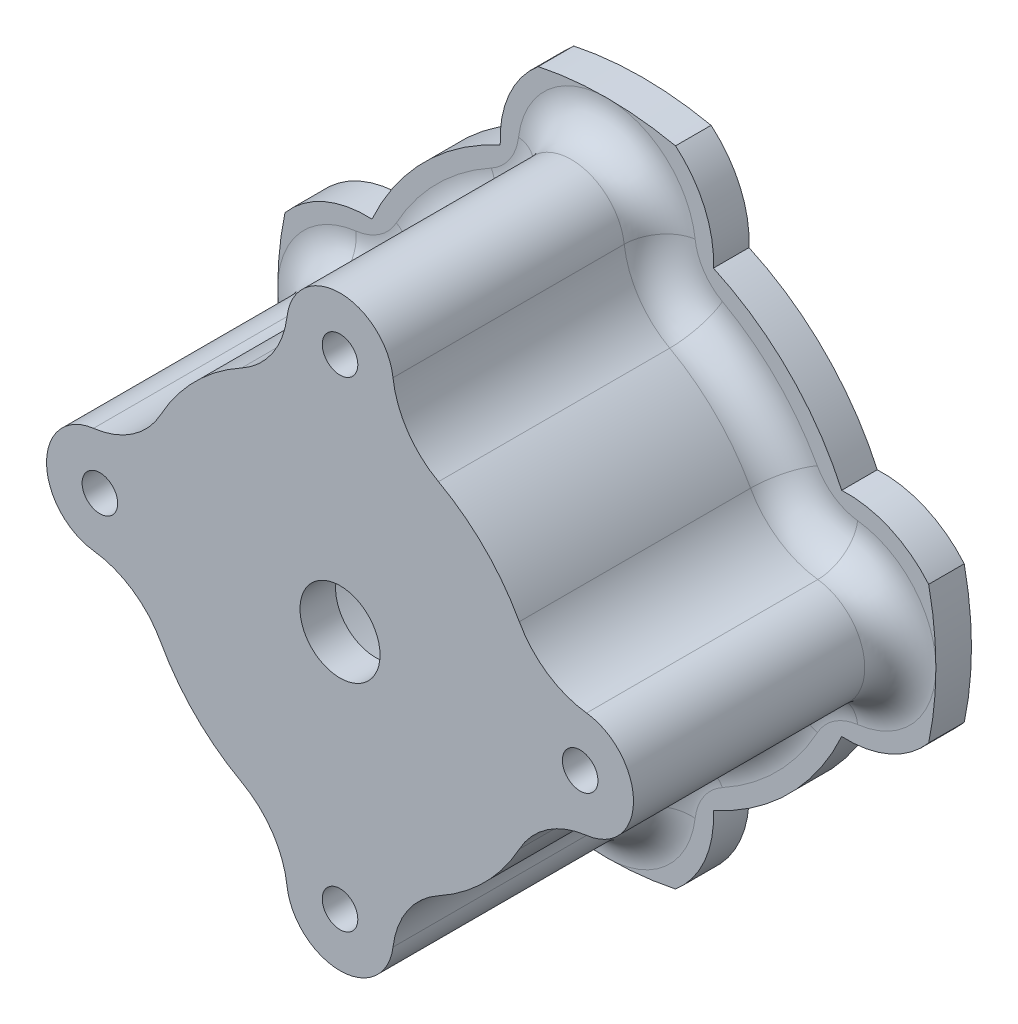
SolidWorks part; units mm, degrees
note: The reader was unsure of these and kept them because the rebuilt part matched: shared geometry of "Sketch2<3>".
ref_plane "Front Plane" through (0, 0, 0) normal (0, 0, 1) x (1, 0, 0)
ref_plane "Top Plane" through (0, 0, 0) normal (0, 1, 0) x (1, 0, 0)
ref_plane "Right Plane" through (0, 0, 0) normal (1, 0, 0) x (0, 0, -1)
sketch "Sketch1" plane through (0, 0, 3) normal (0, 0, 1) x (1, 0, 0)
  line L0 (0, 0) -> (18.5, 0) construction
  line L1 (0, 0) -> (0, -18.5) construction
  circle A1 centre (0, 0) radius 9.5
  circle A6 centre (13.5, 0) radius 1
  circle A7 centre (0, 13.5) radius 1
  circle A8 centre (-13.5, 0) radius 1
  circle A9 centre (0, -13.5) radius 1
  circle A10 centre (0, 13.5) radius 3
  circle A16 centre (-13.5, 0) radius 3
  arc A17 (-3.8611, -18.0926) -> (3.8611, -18.0926) centre (0, 0) ccw
  arc A18 (3.8611, -18.0926) -> (5.9927, -13.2037) centre (0, -13.5) ccw
  arc A19 (5.9927, -13.2037) -> (13.2037, -5.9927) centre (0, 0) ccw
  arc A20 (13.2037, -5.9927) -> (18.0926, -3.8611) centre (13.5, 0) ccw
  arc A21 (18.0926, -3.8611) -> (18.0926, 3.8611) centre (0, 0) ccw
  arc A22 (-18.0926, -3.8611) -> (-18.0926, 3.8611) centre (0, 0) cw
  arc A23 (-13.2037, -5.9927) -> (-18.0926, -3.8611) centre (-13.5, 0) cw
  arc A24 (-5.9927, -13.2037) -> (-13.2037, -5.9927) centre (0, 0) cw
  arc A25 (-3.8611, -18.0926) -> (-5.9927, -13.2037) centre (0, -13.5) cw
  arc A26 (13.2037, 5.9927) -> (18.0926, 3.8611) centre (13.5, 0) cw
  arc A27 (5.9927, 13.2037) -> (13.2037, 5.9927) centre (0, 0) cw
  arc A28 (3.8611, 18.0926) -> (5.9927, 13.2037) centre (0, 13.5) cw
  arc A29 (-3.8611, 18.0926) -> (3.8611, 18.0926) centre (0, 0) cw
  arc A30 (-3.8611, 18.0926) -> (-5.9927, 13.2037) centre (0, 13.5) ccw
  arc A31 (-5.9927, 13.2037) -> (-13.2037, 5.9927) centre (0, 0) ccw
  arc A32 (-13.2037, 5.9927) -> (-18.0926, 3.8611) centre (-13.5, 0) ccw
  circle A33 centre (0, -13.5) radius 3
  circle A34 centre (13.5, 0) radius 3
  circle A35 centre (0, 0) radius 11.5
  circle A36 centre (0, 0) radius 2.25
  dimension "D4" = 4.5
  dimension "D5" = 19
  dimension "D6" = 23
  dimension "D1" = 0
  dimension "D2" = 0
  dimension "D11" = 3.8611
  dimension "D12" = 13.2037
other "AlignGroup1"
other "AlignGroup2"
other "AlignGroup3" parameters "D2"=5.6057, "D3"=6, "D4"=4.5, "D5"=19, "D6"=23, "D7"=2, "D8"=18.5, "D9"=6, "D10"=14.5, "D1"=0, "D11"=3.8611, "D12"=5.9927, "D13"=13.2037, "D14"=13.5, "D15"=18.0926, "D16"=3.8611, "D17"=5.9927, "D18"=13.2037, "D19"=13.5, "D20"=18.0926
other "AlignGroup4"
extrude "Boss-Extrude1" add sketch "Sketch1" along normal blind 2 contours A34 A35 A10 A16 A33 A1 | A16 A35 | A35 A16 A8 | A35 A34 A6 | A35 A33 A9 | A33 A35 | A10 A35 | A35 A10 A7 | A31 A32 A22 A23 A24 A25 A17 A18 A19 A20 A21 A26 A27 A28 A29 A30 A35 A34 A33 A16 A10
sketch "Sketch2" plane through (0, 0, 5) normal (0, 0, 1) x (1, 0, 0)
  arc A0 (-5.5352, 10.0802) -> (-10.0802, 5.5352) centre (0, 0) ccw
  circle A1 centre (0, -13.5) radius 1
  circle A2 centre (0, -13.5) radius 1
  circle A3 centre (-13.5, 0) radius 1
  circle A4 centre (-13.5, 0) radius 1
  circle A5 centre (0, 13.5) radius 1
  circle A6 centre (0, 13.5) radius 1
  circle A7 centre (13.5, 0) radius 1
  circle A8 centre (13.5, 0) radius 1
  circle A9 centre (0, 0) radius 9.5
  circle A10 centre (0, 0) radius 9.5
  circle A11 centre (0, 0) radius 11.5
  arc A12 (-10.0802, -5.5352) -> (-5.5352, -10.0802) centre (0, 0) ccw
  circle A13 centre (13.5, 0) radius 3
  arc A14 (13.8611, -2.9782) -> (13.8611, 2.9782) centre (13.5, 0) ccw
  circle A15 centre (0, -13.5) radius 3
  arc A16 (-2.9782, -13.8611) -> (2.9782, -13.8611) centre (0, -13.5) ccw
  circle A17 centre (-13.5, 0) radius 3
  arc A18 (-13.8611, 2.9782) -> (-13.8611, -2.9782) centre (-13.5, 0) ccw
  circle A19 centre (0, 13.5) radius 3
  arc A20 (2.9782, 13.8611) -> (-2.9782, 13.8611) centre (0, 13.5) ccw
  circle A21 centre (0, 0) radius 2.25
  circle A22 centre (0, 0) radius 2.25
  arc A23 (10.0802, 5.5352) -> (5.5352, 10.0802) centre (0, 0) ccw
  arc A24 (5.5352, -10.0802) -> (10.0802, -5.5352) centre (0, 0) ccw
  arc A25 (-13.8611, -2.9782) -> (-10.0802, -5.5352) centre (-14.463, -7.9418) cw
  arc A26 (-13.8611, 2.9782) -> (-10.0802, 5.5352) centre (-14.463, 7.9418) ccw
  arc A27 (-2.9782, -13.8611) -> (-5.5352, -10.0802) centre (-7.9418, -14.463) ccw
  arc A28 (2.9782, -13.8611) -> (5.5352, -10.0802) centre (7.9418, -14.463) cw
  arc A29 (13.8611, -2.9782) -> (10.0802, -5.5352) centre (14.463, -7.9418) ccw
  arc A30 (13.8611, 2.9782) -> (10.0802, 5.5352) centre (14.463, 7.9418) cw
  arc A31 (-2.9782, 13.8611) -> (-5.5352, 10.0802) centre (-7.9418, 14.463) cw
  arc A32 (-3.8611, -18.0926) -> (3.8611, -18.0926) centre (0, 0) ccw
  arc A33 (3.8611, -18.0926) -> (5.9927, -13.2037) centre (0, -13.5) ccw
  arc A34 (5.9927, -13.2037) -> (13.2037, -5.9927) centre (0, 0) ccw
  arc A35 (13.2037, -5.9927) -> (18.0926, -3.8611) centre (13.5, 0) ccw
  arc A36 (18.0926, -3.8611) -> (18.0926, 3.8611) centre (0, 0) ccw
  arc A37 (18.0926, 3.8611) -> (13.2037, 5.9927) centre (13.5, 0) ccw
  arc A38 (13.2037, 5.9927) -> (5.9927, 13.2037) centre (0, 0) ccw
  arc A39 (5.9927, 13.2037) -> (3.8611, 18.0926) centre (0, 13.5) ccw
  arc A40 (3.8611, 18.0926) -> (-3.8611, 18.0926) centre (0, 0) ccw
  arc A41 (-3.8611, 18.0926) -> (-5.9927, 13.2037) centre (0, 13.5) ccw
  arc A42 (-5.9927, 13.2037) -> (-13.2037, 5.9927) centre (0, 0) ccw
  arc A43 (-13.2037, 5.9927) -> (-18.0926, 3.8611) centre (-13.5, 0) ccw
  arc A44 (-18.0926, 3.8611) -> (-18.0926, -3.8611) centre (0, 0) ccw
  arc A45 (-18.0926, -3.8611) -> (-13.2037, -5.9927) centre (-13.5, 0) ccw
  arc A46 (-13.2037, -5.9927) -> (-5.9927, -13.2037) centre (0, 0) ccw
  arc A47 (-5.9927, -13.2037) -> (-3.8611, -18.0926) centre (0, -13.5) ccw
  arc A48 (-3.8611, -18.0926) -> (3.8611, -18.0926) centre (0, 0) ccw
  arc A49 (3.8611, -18.0926) -> (5.9927, -13.2037) centre (0, -13.5) ccw
  arc A50 (5.9927, -13.2037) -> (13.2037, -5.9927) centre (0, 0) ccw
  arc A51 (13.2037, -5.9927) -> (18.0926, -3.8611) centre (13.5, 0) ccw
  arc A52 (18.0926, -3.8611) -> (18.0926, 3.8611) centre (0, 0) ccw
  arc A53 (18.0926, 3.8611) -> (13.2037, 5.9927) centre (13.5, 0) ccw
  arc A54 (13.2037, 5.9927) -> (5.9927, 13.2037) centre (0, 0) ccw
  arc A55 (5.9927, 13.2037) -> (3.8611, 18.0926) centre (0, 13.5) ccw
  arc A56 (3.8611, 18.0926) -> (-3.8611, 18.0926) centre (0, 0) ccw
  arc A57 (-3.8611, 18.0926) -> (-5.9927, 13.2037) centre (0, 13.5) ccw
  arc A58 (-5.9927, 13.2037) -> (-13.2037, 5.9927) centre (0, 0) ccw
  arc A59 (-13.2037, 5.9927) -> (-18.0926, 3.8611) centre (-13.5, 0) ccw
  arc A60 (-18.0926, 3.8611) -> (-18.0926, -3.8611) centre (0, 0) ccw
  arc A61 (-18.0926, -3.8611) -> (-13.2037, -5.9927) centre (-13.5, 0) ccw
  arc A62 (-13.2037, -5.9927) -> (-5.9927, -13.2037) centre (0, 0) ccw
  arc A63 (-5.9927, -13.2037) -> (-3.8611, -18.0926) centre (0, -13.5) ccw
  arc A64 (2.9782, 13.8611) -> (5.5352, 10.0802) centre (7.9418, 14.463) ccw
  point P76 (2.0555, -11.3148)
  point P81 (11.3148, 2.0555)
  point P84 (-2.0555, 11.3148)
  circle M39 centre (0, -13.5) radius 1
  circle M40 centre (-13.5, 0) radius 1
  circle M41 centre (0, 13.5) radius 1
  circle M58 centre (13.5, 0) radius 1
  dimension "D13" = 5
  dimension "D1" = 0
  dimension "D2" = 0
  dimension "D3" = 0
  dimension "D4" = 0
  dimension "D5" = 0
  dimension "D6" = 0
  dimension "D7" = 0
  dimension "D8" = 0
  dimension "D9" = 0
  dimension "D10" = 0
  dimension "D11" = 0
  dimension "D12" = 0
extrude "Boss-Extrude2" add sketch "Sketch2" along normal blind 15 contours A64 A20 A31 A0 A26 A18 A25 A12 A27 A16 A28 A24 A29 A14 A30 A23 A10 M40 M58 M41 M39 | A10 A22
extrude "Cut-Extrude1" cut sketch "Sketch2<3>" along normal offset from surface 2 and the other way through all contours A10 A22 | A22 up to face at (0, 0, 20)
sketch "Sketch2<3>" plane through (0, 0, 5) normal (0, 0, 1) x (1, 0, 0) same geometry as "Sketch2"
chamfer "Chamfer1" distance 2 angle 45 1 edges at (9.5, 0, 3)
fillet "Fillet1" radius 2 16 edges at (-3.8001, 11.6619, 5) (0, 16.5, 5) (3.8001, 11.6619, 5) (8.1317, 8.1317, 5) (11.6619, 3.8001, 5) (16.5, 0, 5) (11.6619, -3.8001, 5) (8.1317, -8.1317, 5) (3.8001, -11.6619, 5) (0, -16.5, 5) (-3.8001, -11.6619, 5) (-8.1317, -8.1317, 5) (-11.6619, -3.8001, 5) (-16.5, 0, 5) (-11.6619, 3.8001, 5) (-8.1317, 8.1317, 5)
